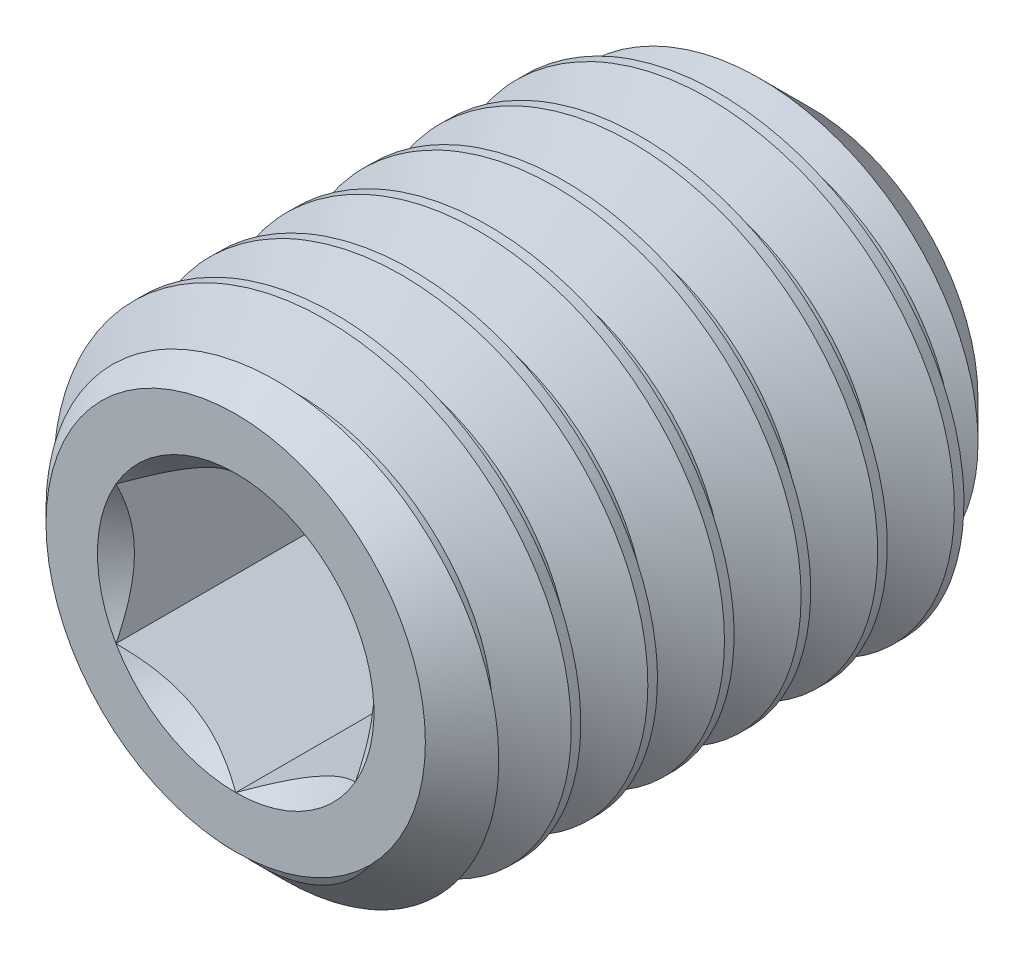
SolidWorks part; units mm, degrees
ref_plane "Front Plane" through (0, 0, 0) normal (0, 0, 1) x (1, 0, 0)
ref_plane "Top Plane" through (0, 0, 0) normal (0, 1, 0) x (1, 0, 0)
ref_plane "Right Plane" through (0, 0, 0) normal (1, 0, 0) x (0, 0, -1)
sketch "Sketch1" plane through (0, 0, 0) normal (1, 0, 0) x (0, 0, -1)
  line L0 (-3, 0) -> (3, 0) construction
  line L1 (-3, -2.5) -> (-3, 2.5) construction
  line L2 (-3, -1.25) -> (-3, 1.25) construction
  line L3 (-3, 2.5) -> (3, 2.5) construction
  line L4 (3, 2.5) -> (3, 0) construction
  line L5 (-3.75, 2.5866) -> (-2.95, 2.5866)
  line L6 (-2.95, 2.5866) -> (-3.35, 1.8938)
  line L7 (-3.35, 1.8938) -> (-3.75, 2.5866)
  line L8 (-3.35, 1.8938) -> (-3.35, 1.9804)
  line L9 (-3.35, 2.5866) -> (-3.35, 2.5)
  line L10 (-3.7, 2.5) -> (-3, 2.5)
  line L11 (-3.725, 2.5433) -> (-2.975, 2.5433)
  line L12 (-3.4, 1.9804) -> (-3.3, 1.9804)
  line L13 (-3, 1.9804) -> (-2.4804, 2.5) construction
  line L14 (-3, -1.9804) -> (-2.4804, -2.5) construction
  line L15 (2.25, 2.5) -> (3, 1.75) construction
  point P3 (-1.8, -2.5)
  point P4 (0, 0)
  point P8 (-3, 0)
  point P11 (-3, 0)
  point P18 (0, 0)
  point P21 (-3.35, 2.5)
  point P24 (-3.35, 2.5433)
  point P27 (-3.35, 1.9804)
  dimension "Length" = 6
  dimension "Thread Size" = 5
  dimension "Drive Size" = 2.5
  dimension "Thread Pitch" = 0.8
  dimension "D2" = 1.2
  dimension "Drive Depth" = 3
  dimension "Drive Side Chamfer Angle" = 90
  dimension "Bottom Chamfer Angle" = 45
  dimension "Bottom Chamfer Diameter" = 3.5
sketch "Sketch2" plane through (0, 0, 0) normal (1, 0, 0) x (0, 0, -1)
  line L0 (2.25, 2.5) -> (3, 1.75) construction
  line L1 (-3, 0) -> (3, 0)
  line L2 (-3, 0) -> (-3, 1.9804)
  line L3 (-2.4804, 2.5) -> (2.25, 2.5)
  line L4 (3, 0) -> (3, 1.75)
  line L5 (-3, 1.9804) -> (-2.4804, 2.5) construction
  line L6 (2.25, 2.5) -> (3, 1.75)
  line L7 (-3, 1.9804) -> (-2.4804, 2.5)
revolve "Revolve1" add sketch "Sketch2" angle 360 about L1
sketch "Sketch3" plane through (0, 0, 3) normal (0, 0, 1) x (1, 0, 0)
  line L0 (0, -1.25) -> (0, 1.25) construction
  line L1 (0, 1.4434) -> (-1.25, 0.7217)
  line L2 (-1.25, 0.7217) -> (-1.25, -0.7217)
  line L3 (-1.25, -0.7217) -> (0, -1.4434)
  line L4 (0, -1.4434) -> (1.25, -0.7217)
  line L5 (1.25, -0.7217) -> (1.25, 0.7217)
  line L6 (1.25, 0.7217) -> (0, 1.4434)
  line L7 (0, -2.5) -> (0, 2.5) construction
  circle A0 centre (0, 0) radius 1.25 construction
extrude "Cut-Extrude1" cut sketch "Sketch3" against normal up to vertex (3 mm away) up to point (0, 0, 0)
sketch "Sketch4" plane through (0, 0, 0) normal (0, 0, 1) x (1, 0, 0)
  line L0 (-1.25, 0.7217) -> (-1.25, -0.7217) construction
  circle A0 centre (0, 0) radius 1.25
extrude "Cut-Extrude2" cut sketch "Sketch4" against normal through all draft 60
sketch "Sketch5" plane through (0, 0, 3) normal (0, 0, 1) x (1, 0, 0)
  line L0 (0, -2.5) -> (0, 2.5) construction
  circle A0 centre (0, 0) radius 1.4434
extrude "Cut-Extrude3" cut sketch "Sketch5" against normal blind 3 draft 45
sketch "Sketch6" plane through (0, 0, 3) normal (0, 0, 1) x (1, 0, 0)
  line L0 (0, -2.5) -> (0, 2.5) construction
  circle A0 centre (0, 0) radius 2.5
curve "Helix/Spiral1" pitch 0.8 height 6.8 radius 2.5 centre (0, 0, 3) axis (0, 0, -1) start towards (0, 1, 0)
sketch "Sketch7" plane through (0, 0, 0) normal (1, 0, 0) x (0, 0, -1)
  line L0 (-3.725, 2.5433) -> (-2.975, 2.5433)
  line L1 (-2.975, 2.5433) -> (-3.3, 1.9804)
  line L2 (-3.3, 1.9804) -> (-3.4, 1.9804)
  line L3 (-3.4, 1.9804) -> (-3.725, 2.5433)
sweep "Cut-Sweep1" cut profiles "Sketch7" path "Helix/Spiral1"
sketch "Sketch8" plane through (0, 0, 0) normal (0, 1, 0) x (1, 0, 0)
  line L0 (0, 3) -> (0, -3) construction
  line L1 (1.75, 3) -> (-1.75, 3) construction
  line L2 (-1.9804, -3) -> (1.9804, -3) construction
ref_axis "Axis1" through (0, 0, -3) along (0, 0, 1)
equation "\"D1@Sketch1\"=\"Thread Pitch@Sketch1\"/8"
equation "\"D1\"= \"Length@Sketch1\" * .438"
equation "\"D4@Helix/Spiral1\"=\"Thread Pitch@Sketch1\""
equation "\"D3@Helix/Spiral1\"=\"Thread Pitch@Sketch1\"+\"Length@Sketch1\""
equation "\"D2@Sketch1\"=\"Thread Pitch@Sketch1\"*1.5"
equation "\"D1@Cut-Extrude3\"=\"Drive Depth@Sketch1\""
